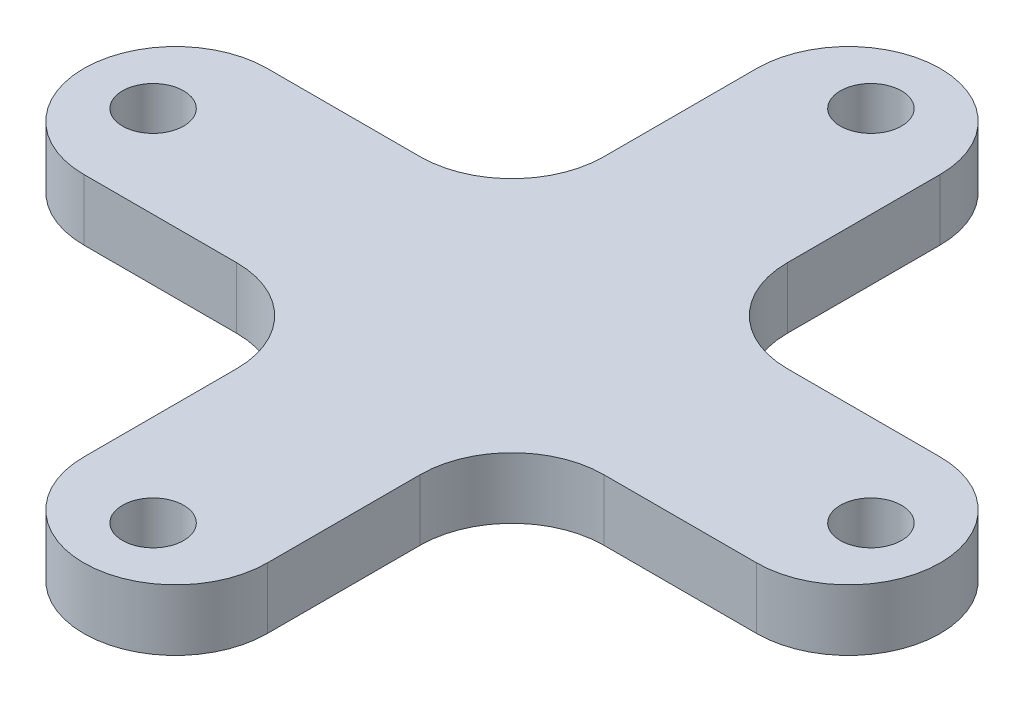
SolidWorks part; units mm, degrees
ref_plane "Piano frontale" through (0, 0, 0) normal (0, 0, 1) x (1, 0, 0)
ref_plane "Piano superiore" through (0, 0, 0) normal (0, 1, 0) x (1, 0, 0)
ref_plane "Piano destro" through (0, 0, 0) normal (1, 0, 0) x (0, 0, -1)
sketch "Schizzo1" plane through (0, 0, 0) normal (0, 1, 0) x (1, 0, 0)
  line L0 (-39.1896, 10.6987) -> (-11.6896, 38.1987) construction
  line L1 (-11.6896, 38.1987) -> (3.3104, 38.1987) construction
  line L2 (-11.6896, 38.1987) -> (-11.6896, -31.8013) construction
  line L3 (-11.6896, -31.8013) -> (3.3104, -31.8013) construction
  line L4 (3.3104, 38.1987) -> (3.3104, -31.8013) construction
  line L5 (-39.1896, 10.6987) -> (30.8104, 10.6987) construction
  line L6 (-39.1896, 10.6987) -> (-39.1896, -4.3013) construction
  line L7 (-39.1896, -4.3013) -> (30.8104, -4.3013) construction
  line L8 (30.8104, 10.6987) -> (30.8104, -4.3013) construction
  line L9 (3.3104, 38.1987) -> (30.8104, 10.6987) construction
  line L10 (30.8104, -4.3013) -> (3.3104, -31.8013) construction
  line L11 (-11.6896, -31.8013) -> (-39.1896, -4.3013) construction
  line L12 (-4.1896, 38.1987) -> (-4.1896, -31.8013) construction
  line L13 (-39.1896, 3.1987) -> (30.8104, 3.1987) construction
  line L14 (-19.1896, -4.3013) -> (-19.1896, -11.8013) construction
  line L15 (-19.1896, -11.8013) -> (-11.6896, -11.8013) construction
  line L16 (-11.6896, -11.8013) -> (-11.6896, -24.3013)
  line L17 (3.3104, -24.3013) -> (3.3104, -11.8013)
  line L18 (10.8104, -4.3013) -> (23.3104, -4.3013)
  line L19 (23.3104, 10.6987) -> (10.8104, 10.6987)
  line L20 (3.3104, 30.6987) -> (3.3104, 18.1987)
  line L21 (-11.6896, 18.1987) -> (-11.6896, 30.6987)
  line L22 (-19.1896, 10.6987) -> (-31.6896, 10.6987)
  line L23 (-31.6896, -4.3013) -> (-19.1896, -4.3013)
  line L24 (-33.5246, 3.1987) -> (-4.1896, 32.5337) construction
  line L25 (-4.1896, 32.5337) -> (25.1454, 3.1987) construction
  line L26 (25.1454, 3.1987) -> (-4.1896, -26.1363) construction
  line L27 (-4.1896, -26.1363) -> (-33.5246, 3.1987) construction
  arc A0 (-31.6896, 10.6987) -> (-31.6896, -4.3013) centre (-31.6896, 3.1987) ccw
  arc A1 (3.3104, 30.6987) -> (-11.6896, 30.6987) centre (-4.1896, 30.6987) ccw
  arc A2 (23.3104, -4.3013) -> (23.3104, 10.6987) centre (23.3104, 3.1987) ccw
  arc A3 (-11.6896, -24.3013) -> (3.3104, -24.3013) centre (-4.1896, -24.3013) ccw
  arc A4 (-19.1896, -4.3013) -> (-11.6896, -11.8013) centre (-19.1896, -11.8013) cw
  arc A5 (-11.6896, 18.1987) -> (-19.1896, 10.6987) centre (-19.1896, 18.1987) cw
  arc A6 (10.8104, 10.6987) -> (3.3104, 18.1987) centre (10.8104, 18.1987) cw
  arc A7 (3.3104, -11.8013) -> (10.8104, -4.3013) centre (10.8104, -11.8013) cw
  circle A8 centre (25.1454, 3.1987) radius 2.5
  circle A9 centre (-33.5246, 3.1987) radius 2.5
  circle A10 centre (-4.1896, 32.5337) radius 2.5
  circle A11 centre (-4.1896, -26.1363) radius 2.5
  point P27 (-4.1896, 3.1987)
  point P40 (-4.1896, 3.1987)
  dimension "D3" = 7.5
  dimension "D4" = 7.5
  dimension "D8" = 5
  dimension "D1" = 70
  dimension "D2" = 15
  dimension "D6" = 7.5
  dimension "D7" = 4
  dimension "D9" = 58.67
  dimension "D5" = 4
extrude "Estrusione-Estrusione1" add sketch "Schizzo1" along normal blind 5
